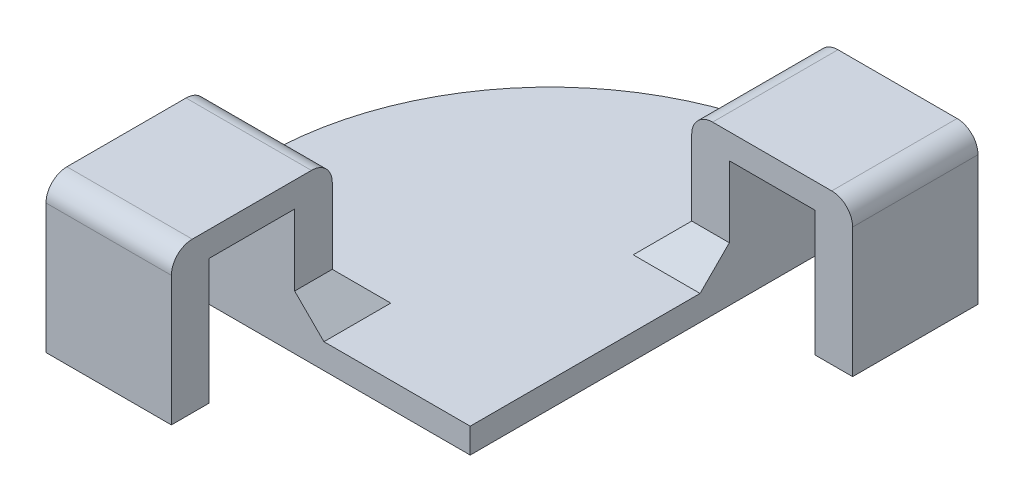
SolidWorks part; units mm, degrees
ref_plane "Front Plane" through (0, 0, 0) normal (0, 0, 1) x (1, 0, 0)
ref_plane "Top Plane" through (0, 0, 0) normal (0, 1, 0) x (1, 0, 0)
ref_plane "Right Plane" through (0, 0, 0) normal (1, 0, 0) x (0, 0, -1)
sketch "Sketch1" plane through (0, 0, 0) normal (0, 1, 0) x (1, 0, 0)
  line L0 (-72, 0) -> (-72, -20.5)
  line L1 (-42, 9) -> (-72, 9)
  line L2 (-42, 9) -> (-42, 0)
  line L3 (-42, 0) -> (-72, 0)
  line L4 (-72, 9) -> (-72, 0)
  line L5 (-9, 92) -> (0, 92)
  line L6 (-9, 92) -> (-9, 62)
  line L7 (-9, 62) -> (0, 62)
  line L8 (0, 92) -> (0, 62)
  line L9 (-72, -20.5) -> (-42, -20.5)
  line L10 (-72, -20.5) -> (-72, -29.5)
  line L11 (-72, -29.5) -> (-42, -29.5)
  line L12 (-42, -20.5) -> (-42, -29.5)
  line L13 (20.5, 92) -> (29.5, 92)
  line L14 (20.5, 92) -> (20.5, 62)
  line L15 (20.5, 62) -> (29.5, 62)
  line L16 (29.5, 92) -> (29.5, 62)
  line L17 (-42, 0) -> (-42, -20.5)
  line L18 (0, 62) -> (20.5, 62)
  line L19 (0, 92) -> (20.5, 92)
  line L20 (0, 99.8961) -> (0, 92)
  line L21 (0, 62) -> (0, 0)
  line L22 (-72, 0) -> (-80.7745, 0)
  line L23 (0, 99.8961) -> (-12.2463, 99.8961)
  line L24 (0, 0) -> (-42, 0)
  line L25 (-80.7745, 0) -> (-80.7745, 31.3679)
  arc A0 (-12.2463, 99.8961) -> (-80.7745, 31.3679) centre (-12.2463, 31.3679) ccw
  point P21 (-9, 125.4006)
  point P22 (-105.8422, 23.2098)
  point P23 (0, 106.4226)
  point P24 (-83.5928, 0)
  point P25 (0, 99.8961)
  point P27 (-80.7745, 31.3679)
  dimension "D1" = 62
  dimension "D2" = 42
  dimension "D3" = 20.5
  dimension "D4" = 30
  dimension "D5" = 9
  dimension "D6" = 9
extrude "Boss-Extrude1" add sketch "Sketch1" along normal blind 6 contours L1 L4 L3 L2 | L8 L5 L6 L7 | L23 A0 L25 L22 L4 L1 L2 L24 L21 L7 L6 L5 L20 region at (-57, 0, -4.5) region at (-37.3094, 0, -45.3563) region at (-4.5, 0, -77)
extrude "Boss-Extrude2" add sketch "Sketch1<3>" along normal blind 24 from surface contours L1 L4 L3 L2 | L8 L5 L6 L7 region at (-57, 0, -4.5) region at (-4.5, 0, -77) starting at face at (-37.5976, 6, -49.0706)
sketch "Sketch1<3>" plane through (0, 0, 0) normal (0, 1, 0) x (1, 0, 0) same geometry as "Sketch1"
extrude "Boss-Extrude3" add sketch "Sketch1<4>" along normal blind 6 from surface contours L1 L4 L3 L2 | L17 L3 L0 L9 | L12 L9 L10 L11 | L8 L5 L6 L7 | L19 L8 L18 L14 | L16 L13 L14 L15 region at (-57, 0, 10.25) region at (-57, 0, -4.5) region at (-57, 0, 25) region at (-4.5, 0, -77) region at (10.25, 0, -77) region at (25, 0, -77) starting at face at (-57, 30, -4.5)
sketch "Sketch1<4>" plane through (0, 0, 0) normal (0, 1, 0) x (1, 0, 0) same geometry as "Sketch1"
extrude "Boss-Extrude4" add sketch "Sketch1<5>" against normal up to surface from surface contours L12 L9 L10 L11 | L16 L13 L14 L15 region at (-57, 0, 25) region at (25, 0, -77) up to face at (-37.5976, 0, -49.0706) starting at face at (-57, 30, 14.75)
sketch "Sketch1<5>" plane through (0, 0, 0) normal (0, 1, 0) x (1, 0, 0) same geometry as "Sketch1"
chamfer "Chamfer1" distance 7 angle 45 6 edges at (-42, 6, -4.5) (-72, 6, -4.5) (-57, 6, -9) (-4.5, 6, -92) (-9, 6, -77) (-4.5, 6, -62)
fillet "Fillet1" radius 5 4 edges at (29.5, 36, -77) (-9, 36, -77) (-57, 36, 29.5) (-57, 36, -9)
